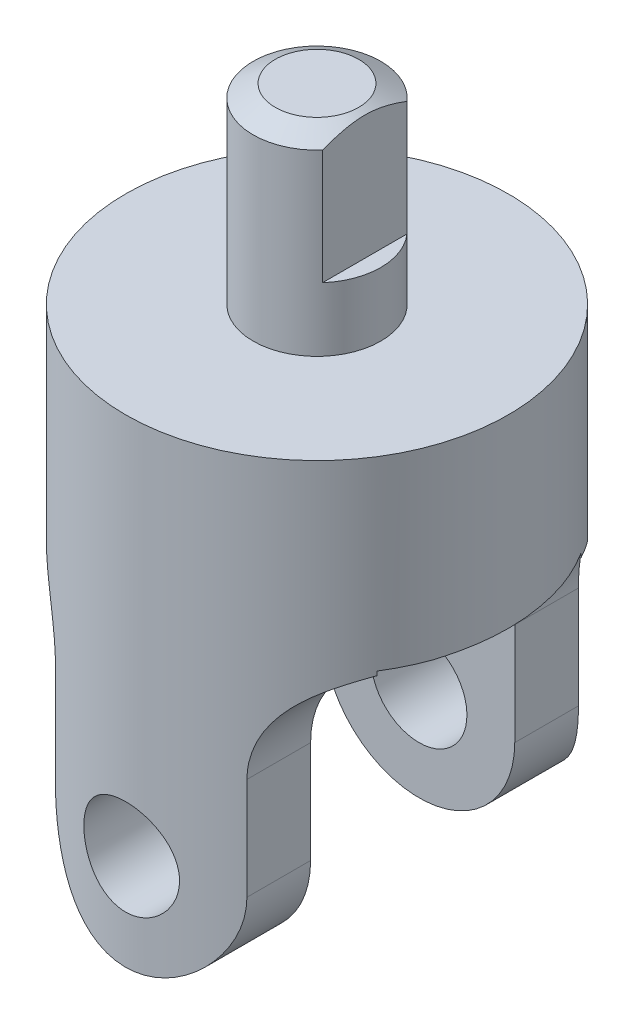
SolidWorks part; units mm, degrees
note: '?' marks a value the reader was unsure of.
ref_plane "Front" through (0, 0, 0) normal (0, 0, 1) x (1, 0, 0)
ref_plane "Top" through (0, 0, 0) normal (0, 1, 0) x (-1, 0, 0)
ref_plane "Right" through (0, 0, 0) normal (1, 0, 0) x (0, 0, -1)
other "Configuration Table"
sketch "Sketch1" plane through (0, 0, 0) normal (0, 1, 0) x (-1, 0, 0)
  circle A0 centre (0, 0) radius 19.05
  dimension "D1" = 38.1
extrude "Base-Extrude" add sketch "Sketch1" along normal blind 47.625
sketch "Sketch2" plane through (0, 0, 0) normal (0, 0, 1) x (1, 0, 0)
  line L0 (0, 0) -> (0, 23.7435) construction
  line L1 (9.525, 9.525) -> (9.525, 19.685)
  line L2 (-9.525, 9.525) -> (-9.525, 19.685)
  line L3 (19.05, 29.21) -> (19.05, -1.3662)
  line L4 (19.05, -1.3662) -> (-19.05, -1.3662)
  line L5 (-19.05, -1.3662) -> (-19.05, 29.21)
  line L6 (19.05, 0) -> (-19.05, 0) construction
  arc A0 (-9.525, 9.525) -> (9.525, 9.525) centre (0, 9.525) ccw
  arc A1 (9.525, 19.685) -> (19.05, 29.21) centre (19.05, 19.685) cw
  arc A2 (-9.525, 19.685) -> (-19.05, 29.21) centre (-19.05, 19.685) ccw
  dimension "D3" = 9.525
  dimension "D1" = 38.1
  dimension "D2" = 19.05
  dimension "D4" = 29.21
extrude "Cut-Extrude1" cut sketch "Sketch2" against normal through all and the other way through all
sketch "Sketch8" plane through (0, 0, 0) normal (1, 0, 0) x (0, 0, -1)
  line L0 (-10.16, -7.4553) -> (10.16, -7.4553)
  line L1 (-10.16, -7.4553) -> (-10.16, 29.1452)
  line L2 (10.16, 29.1452) -> (-10.16, 29.1452)
  line L3 (10.16, 29.1452) -> (10.16, -7.4553)
  point P4 (0, 0)
  dimension "D1" = 10.16
  dimension "D2" = 20.32
extrude "Cut-Extrude5" cut sketch "Sketch8" against normal through all and the other way blind 47.625
sketch "Sketch11" plane through (0, 0, 0) normal (0, 0, 1) x (1, 0, 0)
  circle A0 centre (0, 9.525) radius 4.7625
  dimension "D1" = 9.525
extrude "Cut-Extrude6" cut sketch "Sketch11" against normal through all and the other way through all
sketch "Sketch12" plane through (0, 47.625, 0) normal (0, 1, 0) x (-1, 0, 0)
  circle A0 centre (0, 0) radius 6.35
  dimension "D1" = 12.7
extrude "Boss-Extrude1" add sketch "Sketch12" along normal blind 19.05
chamfer "Chamfer3" distance 1.27 angle 60 1 edges at (0, 66.675, 6.35) first distance on face at (0, 66.675, 6.35)
ref_axis "Axis1" through (0, 97.625, 0) along (0, -1, 0)?
sketch "Sketch13" plane through (0, 66.675, 0) normal (0, 1, 0) x (-1, 0, 0)
  line L0 (-4.7625, 4.2001) -> (-4.7625, -4.2001)
  circle A0 centre (0, 0) radius 6.35 construction
  arc A1 (-4.7625, 4.2001) -> (-4.7625, -4.2001) centre (0, 0) ccw
  dimension "D1" = 1.5875
extrude "Cut-Extrude7" cut sketch "Sketch13" against normal blind 12.7
